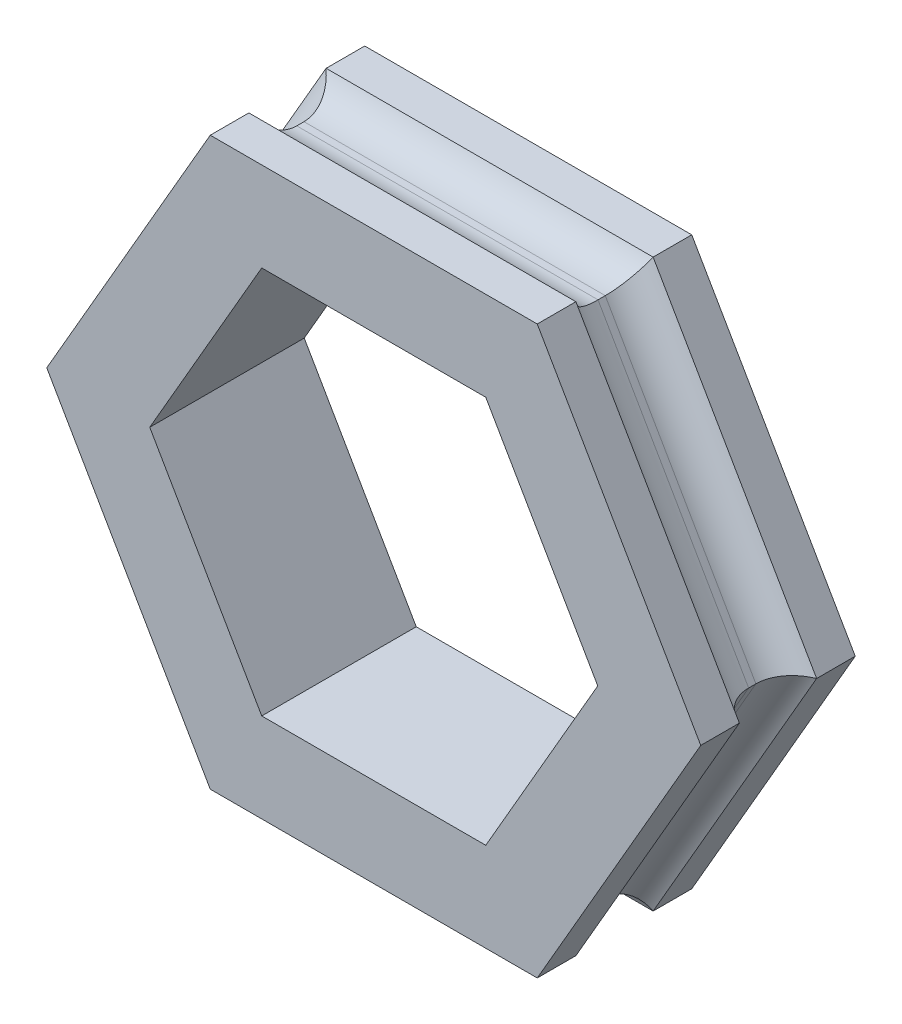
SolidWorks part; units mm, degrees
ref_plane "Front Plane" through (0, 0, 0) normal (0, 0, 1) x (1, 0, 0)
ref_plane "Top Plane" through (0, 0, 0) normal (0, 1, 0) x (1, 0, 0)
ref_plane "Right Plane" through (0, 0, 0) normal (1, 0, 0) x (0, 0, -1)
sketch "Sketch1" plane through (0, 0, 0) normal (0, 0, 1) x (1, 0, 0)
  line L1 (6.35, 0) -> (3.175, 5.4993)
  line L2 (3.175, 5.4993) -> (-3.175, 5.4993)
  line L3 (-3.175, 5.4993) -> (-6.35, 0)
  line L4 (-6.35, 0) -> (-3.175, -5.4993)
  line L5 (-3.175, -5.4993) -> (3.175, -5.4993)
  line L6 (3.175, -5.4993) -> (6.35, 0)
  line L7 (5.85, 0) -> (2.925, 5.0662)
  line L8 (2.925, 5.0662) -> (-2.925, 5.0662)
  line L9 (-2.925, 5.0662) -> (-5.85, 0)
  line L10 (-5.85, 0) -> (-2.925, -5.0662)
  line L11 (-2.925, -5.0662) -> (2.925, -5.0662)
  line L12 (2.925, -5.0662) -> (5.85, 0)
  line L13 (4.35, 0) -> (2.175, 3.7672)
  line L14 (2.175, 3.7672) -> (-2.175, 3.7672)
  line L15 (-2.175, 3.7672) -> (-4.35, 0)
  line L16 (-4.35, 0) -> (-2.175, -3.7672)
  line L17 (-2.175, -3.7672) -> (2.175, -3.7672)
  line L18 (2.175, -3.7672) -> (4.35, 0)
  circle A0 centre (0, 0) radius 5.4993 construction
  circle A1 centre (0, 0) radius 5.0662 construction
  circle A2 centre (0, 0) radius 3.7672 construction
  dimension "D1" = 12.7
  dimension "D2" = 0.5
  dimension "D3" = 1.5
extrude "Boss-Extrude2" add sketch "Sketch1" along normal blind 1.5 and the other way blind 1.5 contours L5 L6 L1 L2 L3 L4 L12 L11 L10 L9 L8 L7 | L11 L12 L7 L8 L9 L10 L18 L17 L16 L15 L14 L13 region at (4.617, -2.6656, 0) region at (4.2535, -2.4557, 0)
extrude "Cut-Extrude1" cut sketch "Sketch1<4>" against normal blind 0.75 and the other way blind 0.75 contours L5 L6 L1 L2 L3 L4 L12 L11 L10 L9 L8 L7 region at (4.617, -2.6656, 0)
sketch "Sketch1<4>" plane through (0, 0, 0) normal (0, 0, 1) x (1, 0, 0) same geometry as "Sketch1"
fillet "Fillet1" radius 0.75 12 edges at (-4.3875, 2.5331, 0.75) (0, 5.0662, 0.75) (4.3875, 2.5331, 0.75) (4.3875, -2.5331, 0.75) (0, -5.0662, 0.75) (-4.3875, -2.5331, 0.75) (-4.3875, -2.5331, -0.75) (-4.3875, 2.5331, -0.75) (0, 5.0662, -0.75) (4.3875, 2.5331, -0.75) (4.3875, -2.5331, -0.75) (0, -5.0662, -0.75)
sketch "Sketch3" plane through (0, 0, 1.5) normal (0, 0, 1) x (1, 0, 0)
  line L0 (-4.35, 0) -> (-5.85, 0.866) construction
  line L1 (-3.175, 5.4993) -> (-6.35, 0) construction
  line L2 (-4.35, 0) -> (-5.85, -0.866) construction
  line L3 (-6.35, 0) -> (-3.175, -5.4993) construction
  line L4 (-2.175, -3.7672) -> (-3.675, -4.6332) construction
  line L5 (-2.175, -3.7672) -> (-2.175, -5.4993) construction
  line L6 (-3.175, -5.4993) -> (3.175, -5.4993) construction
  line L7 (2.175, -3.7672) -> (2.175, -5.4993) construction
  line L8 (2.175, -3.7672) -> (3.675, -4.6332) construction
  line L9 (3.175, -5.4993) -> (6.35, 0) construction
  line L10 (4.35, 0) -> (5.85, -0.866) construction
  line L11 (4.35, 0) -> (5.85, 0.866) construction
  line L12 (6.35, 0) -> (3.175, 5.4993) construction
  line L13 (2.175, 3.7672) -> (3.675, 4.6332) construction
  line L14 (2.175, 3.7672) -> (2.175, 5.4993) construction
  line L15 (3.175, 5.4993) -> (-3.175, 5.4993) construction
  line L16 (-2.175, 3.7672) -> (-3.675, 4.6332) construction
  line L17 (-2.175, 3.7672) -> (-2.175, 5.4993) construction
  circle A0 centre (-2.925, -4.2002) radius 0.375
  circle A1 centre (-5.1, -0.433) radius 0.375
  circle A2 centre (-5.1, 0.433) radius 0.375
  circle A3 centre (-2.925, 4.2002) radius 0.375
  circle A4 centre (-2.175, 4.6332) radius 0.375
  circle A5 centre (2.175, 4.6332) radius 0.375
  circle A6 centre (2.925, 4.2002) radius 0.375
  circle A7 centre (5.1, 0.433) radius 0.375
  circle A8 centre (5.1, -0.433) radius 0.375
  circle A9 centre (2.925, -4.2002) radius 0.375
  circle A10 centre (2.175, -4.6332) radius 0.375
  circle A11 centre (-2.175, -4.6332) radius 0.375
  point P35 (-5.1, -0.433)
  point P37 (-5.1, 0.433)
  point P38 (-2.925, 4.2002)
  point P39 (-2.175, 4.6332)
  point P40 (2.175, 4.6332)
  point P41 (2.925, 4.2002)
  point P42 (5.1, 0.433)
  point P43 (5.1, -0.433)
  point P44 (2.925, -4.2002)
  point P45 (2.175, -4.6332)
  point P46 (-2.925, -4.2002)
  dimension "D1" = 0.75
